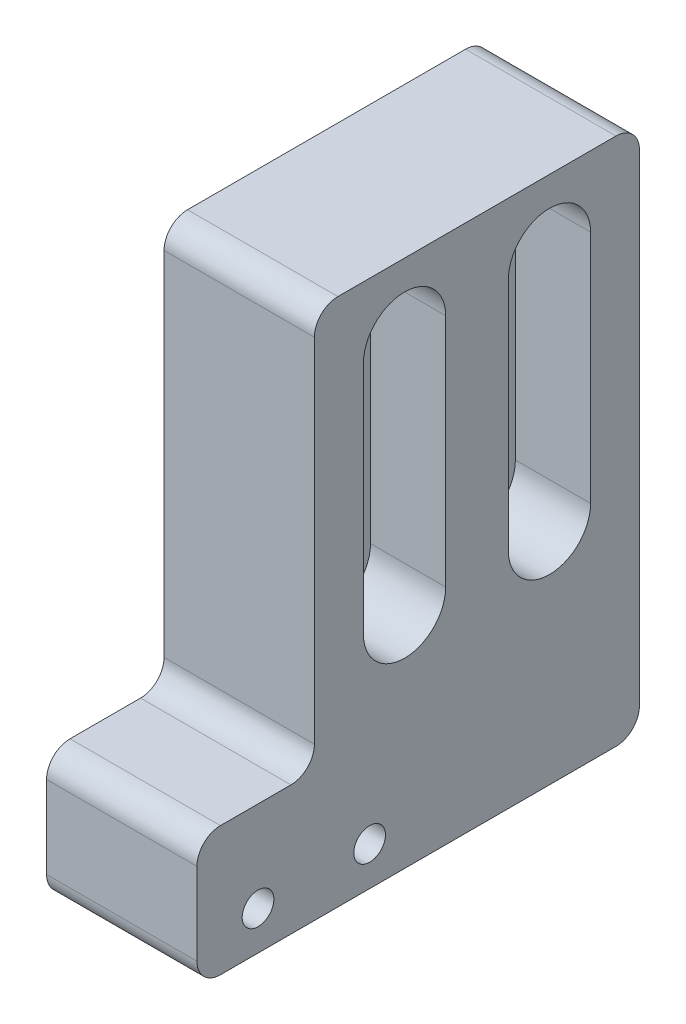
SolidWorks part; units mm, degrees
material "ABS"
ref_plane "Front Plane" through (0, 0, 0) normal (0, 0, 1) x (1, 0, 0)
ref_plane "Top Plane" through (0, 0, 0) normal (0, 1, 0) x (1, 0, 0)
ref_plane "Right Plane" through (0, 0, 0) normal (1, 0, 0) x (0, 0, -1)
sketch "Sketch1" plane through (0, 0, 0) normal (1, 0, 0) x (0, 0, -1)
  line L0 (0, 0) -> (0, 45)
  line L1 (0, 45) -> (-37.6667, 45)
  line L2 (-37.6667, 45) -> (-37.6667, 0)
  line L3 (-37.6667, 0) -> (0, 0)
extrude "Boss-Extrude1" add sketch "Sketch1" against normal blind 12.8
sketch "Sketch2" plane through (-12.8, 0, 0) normal (-1, 0, 0) x (0, 0, 1)
  line L0 (27.6667, 45) -> (27.6667, 11)
  line L1 (27.6667, 11) -> (37.6667, 11)
  line L2 (37.6667, 11) -> (37.6667, 45)
  line L3 (37.6667, 45) -> (27.6667, 45)
extrude "Cut-Extrude1" cut sketch "Sketch2" against normal through all
sketch "Sketch3" plane through (0, 0, 0) normal (1, 0, 0) x (0, 0, -1)
  line L0 (-23.4933, 39) -> (-23.4933, 19)
  line L1 (-16.4933, 19) -> (-16.4933, 39)
  arc A0 (-23.4933, 19) -> (-16.4933, 19) centre (-19.9933, 19) ccw
  arc A1 (-16.4933, 39) -> (-23.4933, 39) centre (-19.9933, 39) ccw
extrude "Cut-Extrude2" cut sketch "Sketch3" against normal blind 6.4
sketch "Sketch4" plane through (-12.8, 0, 0) normal (-1, 0, 0) x (0, 0, 1)
  line L0 (21.4933, 19) -> (21.4933, 39)
  line L1 (18.4933, 39) -> (18.4933, 19)
  arc A0 (18.4933, 19) -> (21.4933, 19) centre (19.9933, 19.0003) ccw
  arc A1 (21.4933, 39) -> (18.4933, 39) centre (19.9933, 39) ccw
extrude "Cut-Extrude3" cut sketch "Sketch4" against normal through all
sketch "Sketch5" plane through (0, 0, 0) normal (1, 0, 0) x (0, 0, -1)
  line L0 (-11.16, 39) -> (-11.16, 19)
  line L1 (-4.16, 19) -> (-4.16, 39)
  arc A0 (-11.16, 19) -> (-4.16, 19) centre (-7.66, 19) ccw
  arc A1 (-4.16, 39) -> (-11.16, 39) centre (-7.66, 39) ccw
extrude "Cut-Extrude4" cut sketch "Sketch5" against normal blind 6.4
sketch "Sketch6" plane through (-12.8, 0, 0) normal (-1, 0, 0) x (0, 0, 1)
  line L0 (6.16, 39) -> (6.16, 19)
  line L1 (9.16, 19) -> (9.16, 39)
  spline S0 degree 3 poles (6.16, 19) (6.16, 18.8323) (6.1889, 18.6624) (6.2445, 18.5042) (6.3, 18.346) (6.3836, 18.1952) (6.4882, 18.0642) (6.5931, 17.933) (6.722, 17.8181) (6.8643, 17.7289) (7.0069, 17.6395) (7.167, 17.5735) (7.3313, 17.5365) (7.4949, 17.4997) (7.6672, 17.4907) (7.8338, 17.5101) (8.0003, 17.5296) (8.1658, 17.5781) (8.3164, 17.6515) (8.4671, 17.725) (8.6071, 17.8254) (8.725, 17.9444) (8.8434, 18.0639) (8.9429, 18.2054) (9.0151, 18.3573) (9.0873, 18.5092) (9.1341, 18.6758) (9.1518, 18.843) (9.1572, 18.8951) (9.16, 18.9476) (9.16, 19) knots 0 0 0 0 0.000503 0.000503 0.000503 0.001006 0.001006 0.001006 0.00151 0.00151 0.00151 0.002015 0.002015 0.002015 0.002518 0.002518 0.002518 0.003021 0.003021 0.003021 0.003524 0.003524 0.003524 0.004028 0.004028 0.004028 0.004533 0.004533 0.004533 0.004688 0.004688 0.004688 0.004688
  spline S1 degree 3 poles (9.16, 39) (9.16, 39.1677) (9.1311, 39.3376) (9.0755, 39.4958) (9.02, 39.654) (8.9364, 39.8048) (8.8318, 39.9358) (8.7269, 40.067) (8.598, 40.1819) (8.4557, 40.2711) (8.3131, 40.3605) (8.153, 40.4265) (7.9887, 40.4635) (7.8251, 40.5003) (7.6528, 40.5093) (7.4862, 40.4899) (7.3197, 40.4704) (7.1542, 40.4219) (7.0036, 40.3485) (6.8529, 40.275) (6.7129, 40.1746) (6.595, 40.0556) (6.4766, 39.9361) (6.3771, 39.7946) (6.3049, 39.6427) (6.2327, 39.4908) (6.1859, 39.3242) (6.1682, 39.157) (6.1628, 39.1049) (6.16, 39.0524) (6.16, 39) knots 0 0 0 0 0.000503 0.000503 0.000503 0.001006 0.001006 0.001006 0.00151 0.00151 0.00151 0.002015 0.002015 0.002015 0.002518 0.002518 0.002518 0.003021 0.003021 0.003021 0.003524 0.003524 0.003524 0.004028 0.004028 0.004028 0.004533 0.004533 0.004533 0.004688 0.004688 0.004688 0.004688
extrude "Cut-Extrude5" cut sketch "Sketch6" against normal through all
hole_wizard "Ø2.7 (2.7) Diameter Hole1" positions "Sketch8" profile "Sketch7" hole size "Ø2.7" standard "ANSI Metric" end condition through all
sketch "Sketch8" plane through (0, 0, 0) normal (1, 0, 0) x (0, 0, -1)
  line L0 (-37.6667, 0) -> (0, 0) construction
  line L1 (-37.6667, 11) -> (-37.6667, 0) construction
  point P0 (-22.9667, 3.3)
  point P1 (-32.4667, 3.3)
  dimension "D1" = 3.3
  dimension "D2" = 5.2
  dimension "D3" = 9.5
sketch "Sketch7" plane through (0, 3.3, 22.9667) normal (0, 1, 0) x (0, 0, -1)
  line L0 (0, 0) -> (0, 12.8)
  line L1 (0, 12.8) -> (1.35, 12.8)
  line L2 (1.35, 12.8) -> (1.35, 0)
  line L5 (1.35, 0) -> (0, 0)
  line L11 (0, -6.35) -> (0, 107.95) construction
  dimension "Thru Hole Dia." = 2.7
  dimension "Thru Hole Depth" = 12.8
fillet "Fillet1" radius 2 6 edges at (-6.4, 0, 37.6667) (-6.4, 45, 0) (-6.4, 0, 0) (-6.4, 11, 27.6667) (-6.4, 45, 27.6667) (-6.4, 11, 37.6667) tangent propagation no
ref_axis "X Axis" through (0, 47.25, 0) along (0, -1, 0)
ref_axis "Y Axis" through (0, 0, 39.55) along (0, 0, -1)
ref_axis "Z Axis" through (-13.44, 0, 0) along (1, 0, 0)
